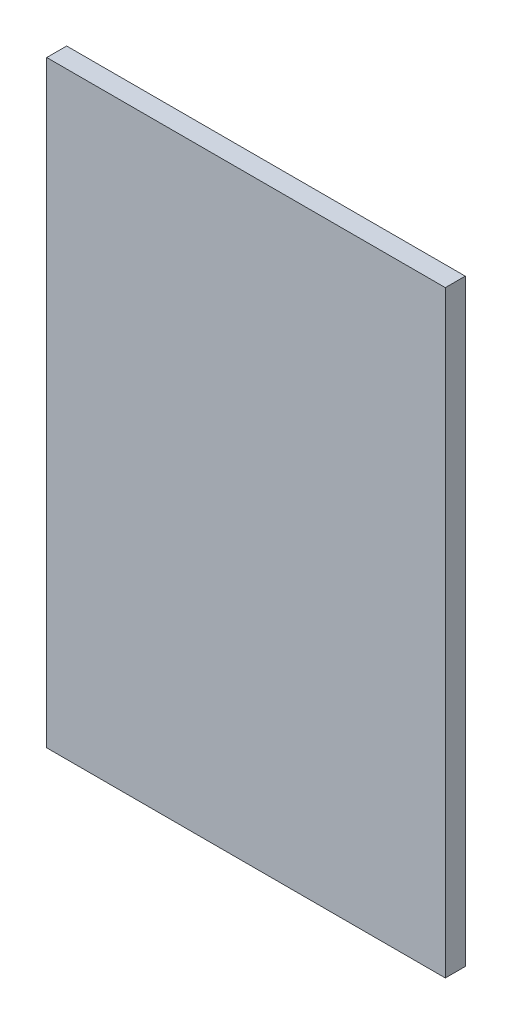
SolidWorks part; units mm, degrees
ref_plane "Front Plane" through (0, 0, 0) normal (0, 0, 1) x (1, 0, 0)
ref_plane "Top Plane" through (0, 0, 0) normal (0, 1, 0) x (1, 0, 0)
ref_plane "Right Plane" through (0, 0, 0) normal (1, 0, 0) x (0, 0, -1)
sketch "Sketch1" plane through (0, 0, 0) normal (0, 0, 1) x (1, 0, 0)
  line L1 (0, 0) -> (200, 0)
  line L2 (0, 0) -> (0, 300)
  line L3 (0, 300) -> (200, 300)
  line L4 (200, 0) -> (200, 300)
  dimension "D1" = 200
  dimension "D2" = 300
extrude "Boss-Extrude1" add sketch "Sketch1" along normal blind 10
sketch "Sketch2" plane through (0, 0, 10) normal (0, 0, 1) x (1, 0, 0)
  line L0 (100, 300) -> (100, 0) construction
  line L1 (200, 300) -> (0, 300) construction
  line L2 (0, 0) -> (200, 0) construction
sketch "Sketch3" plane through (0, 0, 10) normal (0, 0, 1) x (1, 0, 0)
  circle A0 centre (100, 99.6059) radius 4.45
  circle A3 centre (100, 139.6059) radius 4.45
  dimension "D1" = 8.9
  dimension "D2" = 8.9
extrude "Cut-Extrude1" [suppressed] cut sketch "Sketch3" against normal blind 10
sketch "Sketch5" plane through (0, 0, 10) normal (0, 0, 1) x (1, 0, 0)
  line L15 (91.536, 226.6059) -> (43.8, 226.6059)
  line L16 (29.8, 212.6059) -> (29.8, 153.11)
  line L17 (32.4795, 143.11) -> (66.2568, 84.6059)
  line L24 (74.9171, 79.6059) -> (125.0829, 79.6059)
  line L25 (133.7432, 84.6059) -> (167.5205, 143.11)
  line L26 (170.2, 153.11) -> (170.2, 212.6059)
  line L27 (156.2, 226.6059) -> (108.464, 226.6059)
  arc A12 (66.2568, 84.6059) -> (74.9171, 79.6059) centre (74.9171, 89.6059) ccw
  arc A15 (100, 223.7576) -> (91.536, 226.6059) centre (91.536, 212.6059) ccw
  arc A16 (43.8, 226.6059) -> (29.8, 212.6059) centre (43.8, 212.6059) ccw
  arc A17 (29.8, 153.11) -> (32.4795, 143.11) centre (49.8, 153.11) ccw
  arc A25 (125.0829, 79.6059) -> (133.7432, 84.6059) centre (125.0829, 89.6059) ccw
  arc A26 (167.5205, 143.11) -> (170.2, 153.11) centre (150.2, 153.11) ccw
  arc A27 (170.2, 212.6059) -> (156.2, 226.6059) centre (156.2, 212.6059) ccw
  arc A28 (108.464, 226.6059) -> (100, 223.7576) centre (108.464, 212.6059) ccw
extrude "Cut-Extrude2" [suppressed] cut sketch "Sketch5" against normal blind 2
